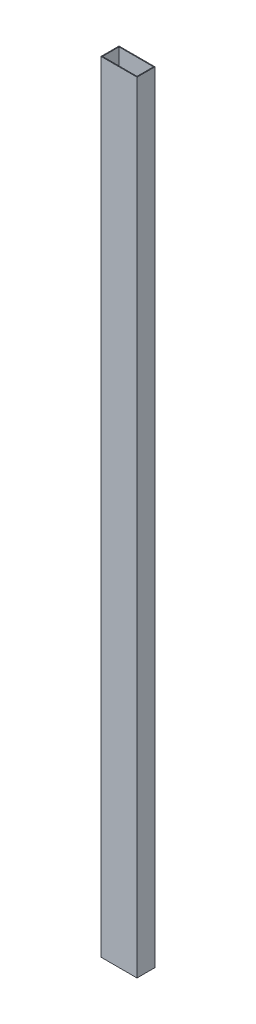
SolidWorks part; units mm, degrees
ref_plane "Front Plane" through (0, 0, 0) normal (0, 0, 1) x (1, 0, 0)
ref_plane "Top Plane" through (0, 0, 0) normal (0, 1, 0) x (1, 0, 0)
ref_plane "Right Plane" through (0, 0, 0) normal (1, 0, 0) x (0, 0, -1)
sketch "Sketch1" plane through (0, 0, 0) normal (0, 1, 0) x (1, 0, 0)
  line L1 (0, 0) -> (-76.2, 0)
  line L2 (0, 0) -> (0, 38.1)
  line L3 (0, 38.1) -> (-76.2, 38.1)
  line L4 (-76.2, 0) -> (-76.2, 38.1)
  line L5 (-74.6125, 1.5875) -> (-1.5875, 1.5875)
  line L6 (-74.6125, 1.5875) -> (-74.6125, 36.5125)
  line L7 (-74.6125, 36.5125) -> (-1.5875, 36.5125)
  line L8 (-1.5875, 1.5875) -> (-1.5875, 36.5125)
  dimension "D1" = 76.2
  dimension "D2" = 38.1
  dimension "D3" = 1.5875
  dimension "D4" = 1.5875
  dimension "D5" = 1.5875
  dimension "D6" = 1.5875
extrude "Boss-Extrude1" add sketch "Sketch1" along normal blind 1651
